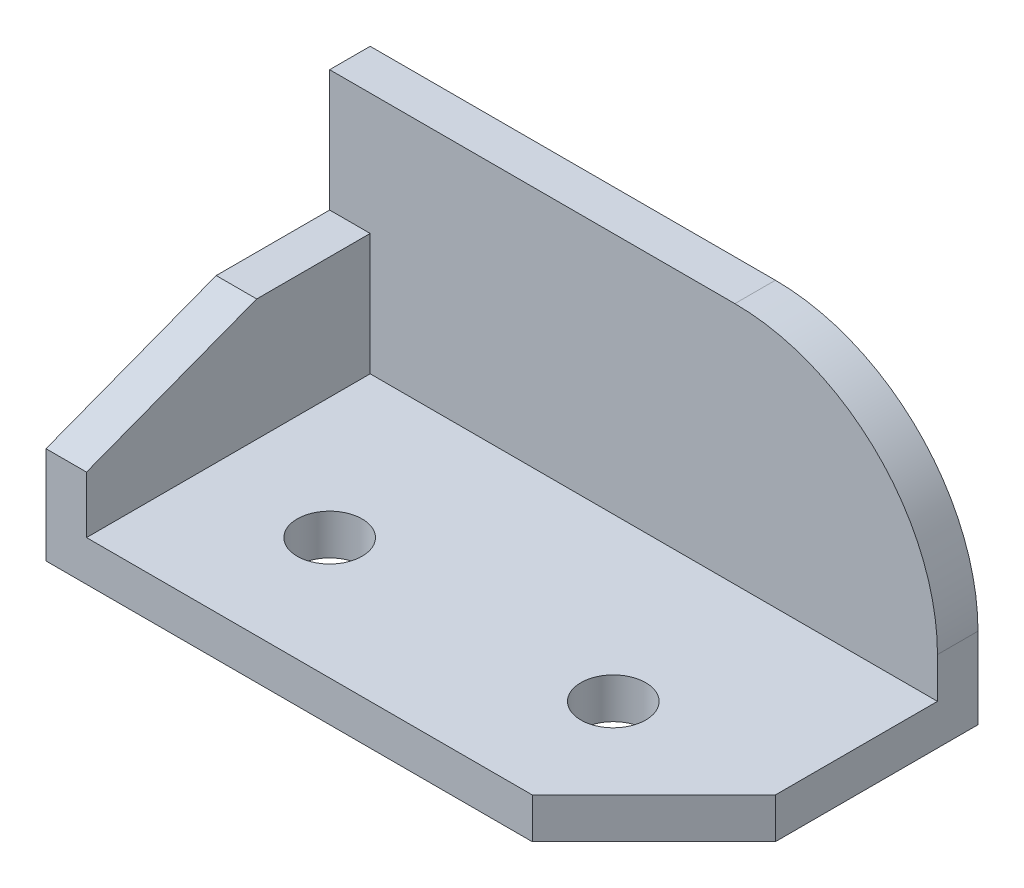
SolidWorks part; units mm, degrees
ref_plane "Front Plane" through (0, 0, 0) normal (0, 0, 1) x (1, 0, 0)
ref_plane "Top Plane" through (0, 0, 0) normal (0, 1, 0) x (1, 0, 0)
ref_plane "Right Plane" through (0, 0, 0) normal (1, 0, 0) x (0, 0, -1)
sketch "Sketch1" plane through (0, 0, 0) normal (1, 0, 0) x (0, 0, -1)
  line L0 (0, 0) -> (-40, 0)
  line L1 (-40, 0) -> (-40, 12)
  line L2 (-40, 12) -> (-19, 20)
  line L3 (-19, 20) -> (-5, 20)
  line L5 (-5, 35) -> (0, 35)
  line L6 (0, 35) -> (0, 0)
  line L7 (-5, 35) -> (-5, 5)
  line L8 (-5, 5) -> (-40, 5)
  dimension "D1" = 35
  dimension "D2" = 40
  dimension "D3" = 20
  dimension "D4" = 21
  dimension "D5" = 5
  dimension "D6" = 12
  dimension "D7" = 5
extrude "Boss-Extrude1" add sketch "Sketch1" along normal blind 75 contours L7 L8 L1 L0 L6 L5 region at (0, 0.5315, 20)
extrude "Boss-Extrude2" add sketch "Sketch1<3>" along normal blind 5 contours L8 L7 L3 L2 L1 region at (0, 11.5794, 20.5)
sketch "Sketch1<3>" plane through (0, 0, 0) normal (1, 0, 0) x (0, 0, -1) same geometry as "Sketch1"
hole_wizard "Hole1" positions "Sketch2" profile "Sketch3" legacy end condition through all
sketch "Sketch2" plane through (0, 5, 0) normal (0, 1, 0) x (1, 0, 0)
  line L0 (75, -40) -> (5, -40) construction
  point P0 (20, -25)
  point P2 (55, -25)
  point P7 (22.9625, -25)
  point P9 (55, -21.7066)
  dimension "D1" = 35
  dimension "D2" = 15
  dimension "D3" = 55
sketch "Sketch3" plane through (20, 5, 25) normal (1, 0, 0) x (0, 0, 1)
  line L0 (0, 0) -> (0, 5)
  line L1 (0, 5) -> (4, 5)
  line L2 (4, 5) -> (4, 0)
  line L3 (4, 0) -> (0, 0)
  line L4 (0, 110) -> (0, -10) construction
  dimension "Diameter" = 8
  dimension "Depth" = 5
chamfer "Chamfer1" distance 15 distance2 15 1 edges at (75, 2.5, 40)
fillet "Fillet1" radius 25 1 edges at (75, 35, 2.5)
